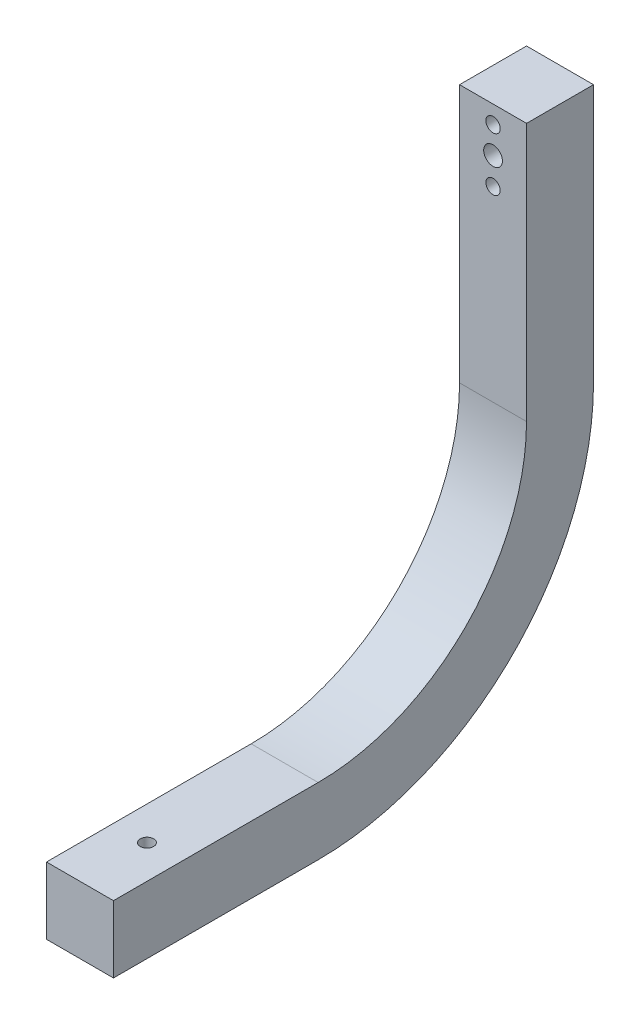
SolidWorks part; units mm, degrees
ref_plane "Front Plane" through (0, 0, 0) normal (0, 0, 1) x (1, 0, 0)
ref_plane "Top Plane" through (0, 0, 0) normal (0, 1, 0) x (1, 0, 0)
ref_plane "Right Plane" through (0, 0, 0) normal (1, 0, 0) x (0, 0, -1)
ref_axis "Z" through (0, 0, 112.875) along (0, 0, -1)
sketch "Sketch1" plane through (0, 0, 0) normal (1, 0, 0) x (0, 0, -1)
  line L0 (-15, 10) -> (0, 10)
  line L1 (0, 10) -> (0, -47.8333)
  line L2 (0, -32) -> (-77.5, -109.5) construction
  line L3 (-61.6667, -109.5) -> (-92.5, -109.5)
  line L4 (-92.5, -109.5) -> (-92.5, -94.5) construction
  line L5 (-92.5, -94.5) -> (-61.6667, -94.5)
  line L6 (-83.7132, -94.5) -> (-15, -25.7868) construction
  line L7 (-15, -47.8333) -> (-15, 10)
  line L8 (-49.3566, -60.1434) -> (-38.75, -70.75) construction
  line L9 (-61.6667, -94.5) -> (-83.7132, -94.5) construction
  line L10 (-92.5, -94.5) -> (-107.5, -94.5)
  line L11 (-92.5, -94.5) -> (-92.5, -109.5) construction
  line L12 (-92.5, -109.5) -> (-107.5, -109.5)
  line L13 (-107.5, -94.5) -> (-107.5, -109.5)
  line L14 (-15, -25.7868) -> (-15, -47.8333) construction
  line L15 (0, -47.8333) -> (0, -32) construction
  line L16 (-77.5, -109.5) -> (-61.6667, -109.5) construction
  arc A0 (-61.6667, -94.5) -> (-15, -47.8333) centre (-61.6667, -47.8333) ccw
  arc A1 (-61.6667, -109.5) -> (0, -47.8333) centre (-61.6667, -47.8333) ccw
  dimension "D1" = 15
  dimension "D2" = 92.5
  dimension "D3" = 109.5
  dimension "D4" = 10
  dimension "D5" = 135
  dimension "D6" = 77.5
  dimension "D7" = 15
  dimension "D8" = 30.8333
extrude "Boss-Extrude1" add sketch "Sketch1" along normal blind 7.5 and the other way blind 7.5
sketch "Sketch3" plane through (0, -94.5, 0) normal (0, 1, 0) x (1, 0, 0)
  line L0 (-8.25, 0) -> (8.25, 0) construction
  line L1 (0, -59.125) -> (0, 59.125) construction
  circle A0 centre (0, -92.5) radius 1.5
  dimension "D2" = 3
  dimension "D1" = 92.5
extrude "Cut-Extrude1" cut sketch "Sketch3" against normal through all
sketch "Sketch4" plane through (0, 0, 15) normal (0, 0, 1) x (1, 0, 0)
  line L0 (0, -6) -> (0, 6) construction
  circle A0 centre (0, 0) radius 2.1
  circle A1 centre (0, 6) radius 1.6
  circle A2 centre (0, -6) radius 1.6
  dimension "D1" = 4.2
  dimension "D3" = 3.2
  dimension "D2" = 12
extrude "Cut-Extrude2" cut sketch "Sketch4" against normal through all both and the other way through all
ref_axis "Axis1" through (0, -94.5, 92.5) along (0, 1, 0)
sketch "Sketch5" plane through (0, -109.5, 0) normal (0, -1, 0) x (1, 0, 0)
  circle A0 centre (0, 92.5) radius 2.275
  dimension "D1" = 4.55
extrude "Cut-Extrude3" cut sketch "Sketch5" against normal blind 6
sketch "Sketch6" plane through (0, -109.5, 0) normal (0, -1, 0) x (1, 0, 0)
  circle A0 centre (0, 92.5) radius 3.825
  dimension "D1" = 7.65
extrude "Cut-Extrude4" cut sketch "Sketch6" against normal blind 0.75
equation "\"rbracket-width\"= \"L2Thickness\""
equation "\"D1@Boss-Extrude1\"=\"rbracket-width\"/2"
equation "\"D2@Boss-Extrude1\"=\"rbracket-width\"/2"
equation "\"EyeCaptureRadius\"= ( \"EyeDiameter\" + \"EyeClearance\" ) / 2"
equation "\"rbracket_planetocenterline_dist\"= \"BasePlaneDistance\""
equation "\"D2@Sketch1\"=\"rbracket_planetocenterline_dist\""
equation "\"EyeDiameter\" = 155"
equation "\"BasePlaneDistance\" = \"EyeDiameter\"/2+15"
equation "\"EyeClearance\" = 2"
equation "\"D1@Sketch1\"=\"rbracket-width\""
equation "\"D3@Sketch1\"=(\"EyeDiameter\"+\"EyeClearance\"+\"EyeClearance\")/2 + \"L2Thickness\" + \"rbracket-width\""
equation "\"D4@Sketch1\"= 10"
equation "\"D6@Sketch1\"=\"EyeDiameter\"/2"
equation "\"D7@Sketch1\"=\"rbracket-width\""
equation "\"D1@Sketch3\"=\"BasePlaneDistance\""
equation "\"L2Thickness\" = 15"
equation "\"D8@Sketch1\"=\"rbracket_planetocenterline_dist\"/3"
equation "\"BearingFlangeOD\"= 7.5"
equation "\"BearingFlangeThickness\"= 0.75"
equation "\"BearingHousingID\"=4.5"
equation "\"BearingDepth\"= 6"
equation "\"D1@Sketch5\"=\"BearingHousingID\" + \"PrinterFilamentThickness\" * \"ApplyPrinterOffsets\" / 2"
equation "\"D1@Cut-Extrude3\"=\"BearingDepth\""
equation "\"D1@Sketch6\"=\"BearingFlangeOD\" + \"PrinterFilamentThickness\" * 1.5 * \"ApplyPrinterOffsets\""
equation "\"D1@Cut-Extrude4\"=\"BearingFlangeThickness\""
equation "\"PrinterFilamentThickness\"= 0.1"
equation "\"ApplyPrinterOffsets\"= 1"
